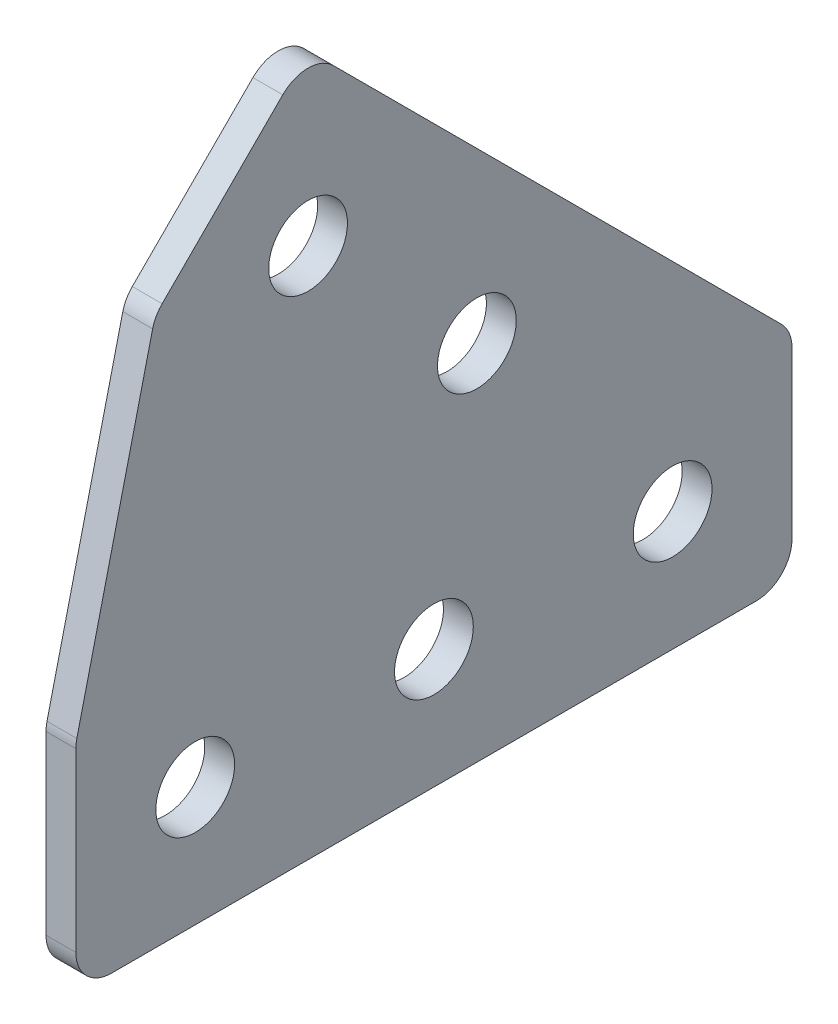
SolidWorks part; units mm, degrees
material "Chrome Stainless Steel"
ref_plane "Front Plane" through (0, 0, 0) normal (0, 0, 1) x (1, 0, 0)
ref_plane "Top Plane" through (0, 0, 0) normal (0, 1, 0) x (1, 0, 0)
ref_plane "Right Plane" through (0, 0, 0) normal (1, 0, 0) x (0, 0, -1)
sketch "Sketch1" plane through (0, 0, 0) normal (1, 0, 0) x (0, 0, -1)
  line L0 (0, 0) -> (-350, 350) construction
  line L1 (-350, 350) -> (-350, 0) construction
  line L2 (-350, 0) -> (0, 0) construction
  line L3 (-78.1401, 0) -> (-18.1401, 0)
  line L4 (-18.1401, 0) -> (-18.1401, 18.1401)
  line L5 (-18.1401, 18.1401) -> (-58.6831, 58.6831)
  line L6 (-58.6831, 58.6831) -> (-71.5101, 45.8561)
  line L7 (-78.1401, 0) -> (-78.1401, 18.1401)
  line L8 (-78.1401, 18.1401) -> (-71.5101, 45.8561)
  point P6 (-90.8721, 25.9943)
  point P11 (-83.61, 42.5305)
  dimension "D1" = 350
  dimension "D2" = 350
  dimension "D3" = 60
extrude "Boss-Extrude1" add sketch "Sketch1" along normal blind 2.5
sketch "Sketch2" plane through (2.5, 0, 0) normal (1, 0, 0) x (0, 0, -1)
  line L0 (-78.1401, 0) -> (-18.1401, 0) construction
  line L1 (-18.1401, 18.1401) -> (-58.6831, 58.6831) construction
  line L2 (-58.6831, 58.6831) -> (-71.5101, 45.8561) construction
  line L5 (-18.1401, 0) -> (-18.1401, 18.1401) construction
  circle A0 centre (-28.1401, 10) radius 3.3
  circle A1 centre (-58.6831, 44.5409) radius 3.3
  point P10 (-27.7581, 10)
  point P14 (-53.7436, -4.8846)
  dimension "D1" = 6.6
  dimension "D3" = 6.6
  dimension "D2" = 10
  dimension "D4" = 10
  dimension "D5" = 10
  dimension "D6" = 10
extrude "Cut-Extrude1" cut sketch "Sketch2" against normal through all contours A0 region at (2.5, 10, 28.1401)
pattern_linear "LPattern1" count 3 spacing 20 along (0, 0, 1) of "Cut-Extrude1"
extrude "Cut-Extrude2" cut sketch "Sketch2<4>" against normal through all contours A1 region at (2.5, 44.5409, 58.6831)
sketch "Sketch2<4>" plane through (2.5, 0, 0) normal (1, 0, 0) x (0, 0, -1) same geometry as "Sketch2"
pattern_linear "LPattern2" count 2 spacing 20 along (0, -0.7071, -0.7071) of "Cut-Extrude2"
fillet "Fillet1" radius 3 6 edges at (1.25, 0, 18.1401) (1.25, 18.1401, 18.1401) (1.25, 58.6831, 58.6831) (1.25, 0, 78.1401) (1.25, 18.1401, 78.1401) (1.25, 45.8561, 71.5101)
